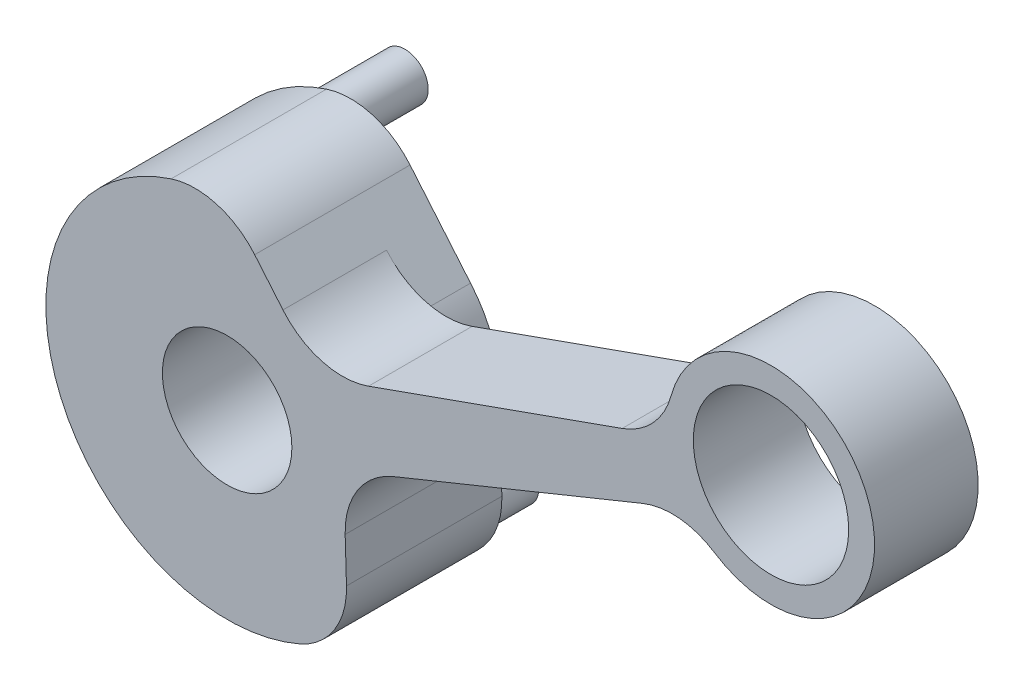
SolidWorks part; units mm, degrees
ref_plane "Front Plane" through (0, 0, 0) normal (0, 0, 1) x (1, 0, 0)
ref_plane "Top Plane" through (0, 0, 0) normal (0, 1, 0) x (1, 0, 0)
ref_plane "Right Plane" through (0, 0, 0) normal (1, 0, 0) x (0, 0, -1)
sketch "Sketch1" plane through (0, 0, 0) normal (0, 0, 1) x (1, 0, 0)
  line L0 (0, 0) -> (21, 0) construction
  line L1 (21, 0) -> (21, 8) construction
  line L2 (0, 0) -> (21, 8) construction
  line L3 (0, 0) -> (21, 8)
  line L7 (0.534, -1.4017) -> (-0.534, 1.4017)
  line L8 (21.356, 7.0655) -> (20.644, 8.9345)
  line L11 (-0.534, 1.4017) -> (20.644, 8.9345)
  line L12 (0.534, -1.4017) -> (21.356, 7.0655)
  line L13 (0, 0) -> (0, 7) construction
  line L14 (1.0632, 5.7329) -> (3.4949, 2.8348)
  line L15 (4.6081, -3.5724) -> (4.4951, 0.2091)
  arc A0 (-2.1612, 6.658) -> (2.8164, -6.4084) centre (0, 0) ccw
  circle A1 centre (21, 8) radius 4
  circle A2 centre (21, 8) radius 3
  circle A3 centre (0, 0) radius 4.5
  arc A4 (6.8987, 1.1865) -> (5.9395, 3.7043) centre (0, 0) ccw
  arc A5 (2.8164, -6.4084) -> (4.6081, -3.5724) centre (1.6094, -3.6619) ccw
  arc A6 (1.0632, 5.7329) -> (-2.1612, 6.658) centre (-1.235, 3.8046) ccw
  point P19 (4.6574, -5.2257)
  dimension "D1" = 14
  dimension "D4" = 8
  dimension "D5" = 6
  dimension "D11" = 9
  dimension "D12" = 3
  dimension "D2" = 21
  dimension "D3" = 8
  dimension "D6" = 90
  dimension "D7" = 1.5
  dimension "D8" = 90
  dimension "D9" = 1
  dimension "D10" = 3
  dimension "D13" = 20.854
extrude "Boss-Extrude1" add sketch "Sketch1" along normal blind 4 contours L11 A0 L12 L7 | L3 A0 L11 L7 | L12 A0 L3 L7 | A1 L11 A0 L3 | A1 L3 A0 L12 | A2 L3 A1 L12 | A2 L11 A1 L3 | A2 L12 A1 L11 | L14 A6 A0 A5 L15 A3 | L3 A4 L11 A3 | L12 A4 L3 A3 region at (1.7888, 1.4519, 0) region at (2.3014, 0.1063, 0) region at (-0.5172, -0.197, 0) region at (5.0636, 2.6691, 0) region at (5.556, 1.3764, 0) region at (11.496, 5.0354, 0) region at (11.9324, 3.8897, 0) region at (17.5887, 7.2799, 0) region at (17.9742, 6.2678, 0) region at (4.3735, -1.7618, 0) region at (20.8269, 11.883, 0)
fillet "Fillet1" radius 3 2 edges at (3.4949, 2.8348, 2) (4.4951, 0.2091, 2)
fillet "Fillet2" radius 3 2 edges at (17.7889, 5.6149, 2) (17.0159, 7.644, 2)
extrude "Boss-Extrude2" add sketch "Sketch1<3>" against normal blind 2 contours L14 A6 A0 A5 L15 A3 | A3 region at (4.3735, -1.7618, 0)
sketch "Sketch1<3>" plane through (0, 0, 0) normal (0, 0, 1) x (1, 0, 0) same geometry as "Sketch1"
sketch "Sketch2" plane through (0, 0, 4) normal (0, 0, 1) x (1, 0, 0)
  circle A0 centre (0, 0) radius 2.5
  dimension "D1" = 5
extrude "Cut-Extrude1" cut sketch "Sketch2" against normal through all
sketch "Sketch4" plane through (0, 0, -2) normal (0, 0, 1) x (1, 0, 0)
  line L0 (0, 0) -> (21, 0) construction
  line L1 (21, 0) -> (21, 8) construction
  line L2 (0, 0) -> (21, 8) construction
  line L3 (0, 0) -> (-2.136, 5.6069) construction
  circle A0 centre (-2.136, 5.6069) radius 0.9
  circle A7 centre (5.6069, 2.136) radius 0.9
  circle A8 centre (2.136, -5.6069) radius 0.9
  circle A9 centre (-5.6069, -2.136) radius 0.9
  point P15 (0, 0)
  point P16 (-0.6452, 0.2892)
  point P17 (0, 0)
  dimension "D3" = 90
  dimension "D5" = 1.8
  dimension "D1" = 21
  dimension "D2" = 8
  dimension "D6" = 6
  dimension "D4" = 20.854
  dimension "D7" = 4
extrude "Boss-Extrude3" add sketch "Sketch4" against normal blind 3 contours A9 | A8 | A0 region at (2.136, -5.6069, -2) region at (-5.6069, -2.136, -2)
